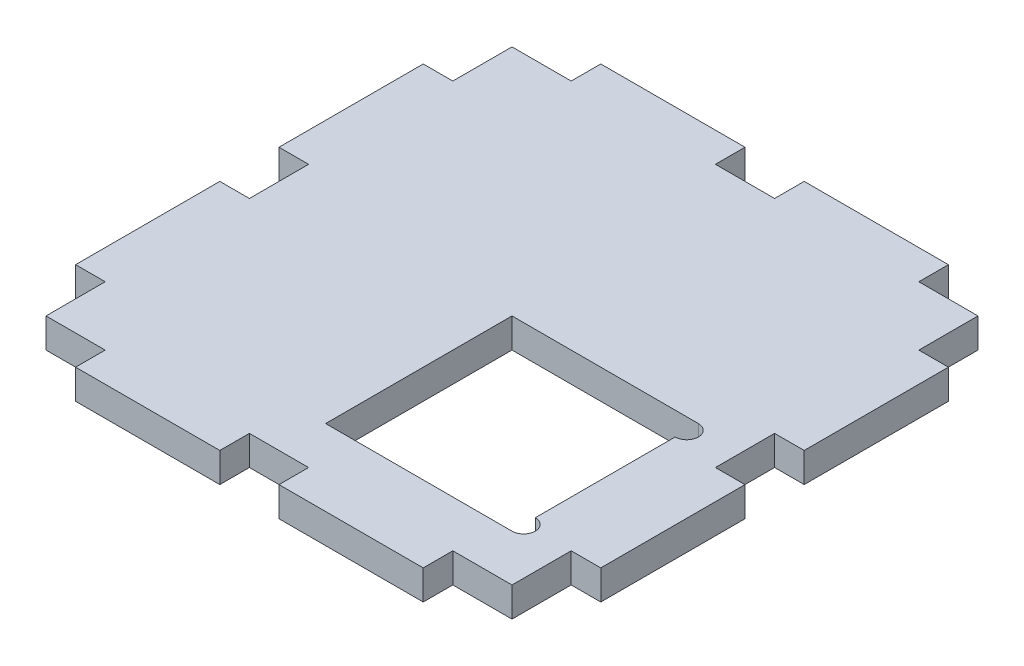
SolidWorks part; units mm, degrees
note: '?' marks a value the reader was unsure of.
material "Acrylic (Medium-high impact)"
ref_plane "Front Plane" through (0, 0, 0) normal (0, 0, 1) x (1, 0, 0)
ref_plane "Top Plane" through (0, 0, 0) normal (0, 1, 0) x (1, 0, 0)
ref_plane "Right Plane" through (0, 0, 0) normal (1, 0, 0) x (0, 0, -1)
sketch "Sketch1" plane through (0, 0, 0) normal (0, 1, 0) x (1, 0, 0)
  line L1 (-56.35, -56.35) -> (56.35, -56.35)
  line L2 (-56.35, -56.35) -> (-56.35, 56.35)
  line L3 (-56.35, 56.35) -> (56.35, 56.35)
  line L4 (56.35, -56.35) -> (56.35, 56.35)
  line L5 (-56.35, -56.35) -> (56.35, 56.35) construction
  line L6 (-56.35, 56.35) -> (56.35, -56.35) construction
  point P0 (0, 0)
  dimension "D1" = 112.7
  dimension "D2" = 112.7
extrude "Boss-Extrude1" add sketch "Sketch1" along normal blind 6.35
sketch "Sketch2" plane through (0, 6.35, 0) normal (0, 1, 0) x (1, 0, 0)
  line L0 (-6.35, 50) -> (-6.35, 56.35)
  line L1 (-6.35, 50) -> (6.35, 50)
  line L2 (-6.35, 56.35) -> (6.35, 56.35)
  line L3 (6.35, 50) -> (6.35, 56.35)
  line L4 (-6.35, 50) -> (6.35, 56.35) construction
  line L5 (-6.35, 56.35) -> (6.35, 50) construction
  line L6 (-56.35, 56.35) -> (-56.35, -56.35) construction
  line L7 (56.35, 56.35) -> (-56.35, 56.35) construction
  point P1 (0, 53.175)
  dimension "D1" = 6.35
  dimension "D2" = 12.7
  dimension "D3" = 56.35
  dimension "D4" = 3.175
ref_point "Point1"
extrude "Cut-Extrude2" cut sketch "Sketch2" against normal through all
ref_axis "Axis1" through (0, 6.35, 0) along (0, 1, 0)?
pattern_circular "CirPattern1" count 4 every 90 about axis through (0, 0, 0) along (0, 1, 0) of "Cut-Extrude2"
sketch "Sketch4" plane through (0, 6.35, 0) normal (0, 1, 0) x (1, 0, 0)
  line L1 (-50, -50) -> (50, -50)
  line L2 (-50, -50) -> (-50, 50)
  line L3 (-50, 50) -> (50, 50)
  line L4 (50, -50) -> (50, 50)
  line L5 (-50, -50) -> (50, 50) construction
  line L6 (-50, 50) -> (50, -50) construction
  point P0 (0, 0)
  dimension "D1" = 100
  dimension "D2" = 100
sketch "Sketch5" plane through (0, 6.35, 0) normal (0, 1, 0) x (1, 0, 0)
  line L0 (50, -50) -> (50, 50) construction
  line L1 (56.35, -56.35) -> (50, -56.35)
  line L2 (56.35, -56.35) -> (56.35, -37.3)
  line L3 (56.35, -37.3) -> (50, -37.3)
  line L4 (50, -56.35) -> (50, -37.3)
  dimension "D1" = 19.05
extrude "Cut-Extrude3" cut sketch "Sketch5" against normal through all
sketch "Sketch6" plane through (0, 6.35, 0) normal (0, 1, 0) x (1, 0, 0)
  line L0 (-50, -50) -> (50, -50) construction
  line L1 (50, -56.35) -> (37.3, -56.35)
  line L2 (50, -56.35) -> (50, -50)
  line L3 (50, -50) -> (37.3, -50)
  line L4 (37.3, -56.35) -> (37.3, -50)
  dimension "D1" = 12.7
extrude "Cut-Extrude4" cut sketch "Sketch6" against normal through all
pattern_circular "CirPattern2" count 4 every 90 about axis through (0, 0, 0) along (0, 1, 0) of "Cut-Extrude3"
pattern_circular "CirPattern3" count 4 every 90 about axis through (0, 0, 0) along (0, 1, 0) of "Cut-Extrude4"
sketch "Sketch7" plane through (0, 6.35, 0) normal (0, 1, 0) x (1, 0, 0)
  line L0 (-50, 50) -> (50, -50) construction
  line L1 (0, 0) -> (40, 0)
  line L2 (0, 0) -> (0, -40)
  line L3 (0, -40) -> (40, -40)
  line L4 (40, 0) -> (40, -40)
  dimension "D1" = 40
extrude "Cut-Extrude5" cut sketch "Sketch7" against normal through all
ref_point "Point3"
ref_axis "Axis3" through (20, 3.175, 0) along (0, 0, 1)?
ref_point "Point4"
ref_plane "Plane1" through (0, 3.175, 20) normal (0, 0, 1) x (1, 0, 0)
sketch "Sketch8" plane through (0, 6.35, 0) normal (0, 1, 0) x (1, 0, 0)
  line L0 (40, -40) -> (40, 0) construction
  arc A0 (40, -40) -> (40, -35) centre (40, -37.5) ccw
  dimension "D1" = 2.5
  dimension "D2" = 5
extrude "Cut-Extrude6" cut sketch "Sketch8" against normal through all and the other way through all
mirror "Mirror1" about plane through (0, 3.175, 20) normal (0, 0, 1) of "Cut-Extrude6"
